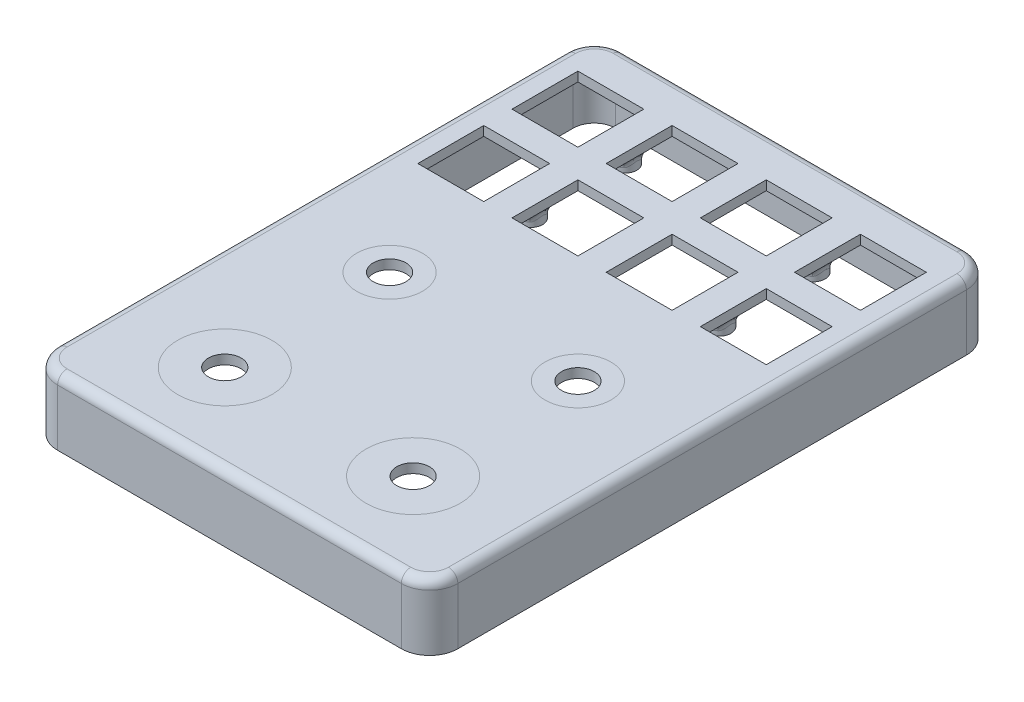
SolidWorks part; units mm, degrees
ref_plane "Plan de face" through (0, 0, 0) normal (0, 0, 1) x (1, 0, 0)
ref_plane "Plan de dessus" through (0, 0, 0) normal (0, 1, 0) x (1, 0, 0)
ref_plane "Plan de droite" through (0, 0, 0) normal (1, 0, 0) x (0, 0, -1)
sketch "Esquisse1" plane through (0, 0, 0) normal (0, 1, 0) x (1, 0, 0)
  line L1 (-42.5, -60) -> (42.5, -60)
  line L2 (-42.5, -60) -> (-42.5, 60)
  line L3 (-42.5, 60) -> (42.5, 60)
  line L4 (42.5, -60) -> (42.5, 60)
  line L5 (-42.5, -60) -> (42.5, 60) construction
  line L6 (-42.5, 60) -> (42.5, -60) construction
  point P0 (0, 0)
  dimension "D1" = 85
  dimension "D2" = 120
extrude "Boss.-Extru.1" add sketch "Esquisse1" along normal blind 2
sketch "Esquisse2" plane through (0, 2, 0) normal (0, 1, 0) x (1, 0, 0)
  line L0 (42.5, 60) -> (-42.5, 60) construction
  line L1 (-37, 51) -> (-23, 51)
  line L2 (-37, 51) -> (-37, 37)
  line L3 (-37, 37) -> (-23, 37)
  line L4 (-23, 51) -> (-23, 37)
  line L5 (-37, 51) -> (-23, 37) construction
  line L6 (-37, 37) -> (-23, 51) construction
  line L7 (-17, 51) -> (-3, 51)
  line L8 (-17, 51) -> (-17, 37)
  line L9 (-17, 37) -> (-3, 37)
  line L10 (-3, 51) -> (-3, 37)
  line L11 (-17, 51) -> (-3, 37) construction
  line L12 (-17, 37) -> (-3, 51) construction
  line L13 (3, 51) -> (17, 51)
  line L14 (3, 51) -> (3, 37)
  line L15 (3, 37) -> (17, 37)
  line L16 (17, 51) -> (17, 37)
  line L17 (3, 51) -> (17, 37) construction
  line L18 (3, 37) -> (17, 51) construction
  line L19 (23, 51) -> (37, 51)
  line L20 (23, 51) -> (23, 37)
  line L21 (23, 37) -> (37, 37)
  line L22 (37, 51) -> (37, 37)
  line L23 (23, 51) -> (37, 37) construction
  line L24 (23, 37) -> (37, 51) construction
  line L25 (23, 31) -> (37, 31)
  line L26 (23, 31) -> (23, 17)
  line L27 (23, 17) -> (37, 17)
  line L28 (37, 31) -> (37, 17)
  line L29 (23, 31) -> (37, 17) construction
  line L30 (23, 17) -> (37, 31) construction
  line L31 (17, 31) -> (3, 31)
  line L32 (17, 31) -> (17, 17)
  line L33 (17, 17) -> (3, 17)
  line L34 (3, 31) -> (3, 17)
  line L35 (17, 31) -> (3, 17) construction
  line L36 (17, 17) -> (3, 31) construction
  line L37 (-3, 31) -> (-17, 31)
  line L38 (-3, 31) -> (-3, 17)
  line L39 (-3, 17) -> (-17, 17)
  line L40 (-17, 31) -> (-17, 17)
  line L41 (-3, 31) -> (-17, 17) construction
  line L42 (-3, 17) -> (-17, 31) construction
  line L43 (-37, 31) -> (-23, 31)
  line L44 (-37, 31) -> (-37, 17)
  line L45 (-37, 17) -> (-23, 17)
  line L46 (-23, 31) -> (-23, 17)
  line L47 (-37, 31) -> (-23, 17) construction
  line L48 (-37, 17) -> (-23, 31) construction
  point P0 (-30, 44)
  point P5 (-10, 44)
  point P10 (10, 44)
  point P15 (30, 44)
  point P20 (30, 24)
  point P25 (10, 24)
  point P30 (-10, 24)
  point P35 (-30, 24)
  dimension "D1" = 14
  dimension "D2" = 14
  dimension "D3" = 20
  dimension "D4" = 20
  dimension "D5" = 20
  dimension "D6" = 10
  dimension "D7" = 16
  dimension "D8" = 20
extrude "Enlèv. mat.-Extru.1" cut sketch "Esquisse2" against normal blind 2
sketch "Esquisse3" plane through (0, 2, 0) normal (0, 1, 0) x (1, 0, 0)
  circle A0 centre (-20, -6) radius 7
  circle A1 centre (-20, -41) radius 10
  circle A2 centre (20, -6) radius 7
  circle A3 centre (20, -41) radius 10
  dimension "D1" = 14
  dimension "D6" = 20
  dimension "D2" = 35
  dimension "D3" = 20
  dimension "D4" = 20
  dimension "D5" = 6
extrude "Enlèv. mat.-Extru.2" cut sketch "Esquisse3" against normal blind 2
fillet "Congé1" radius 6 4 edges at (42.5, 1, 60) (-42.5, 1, 60) (-42.5, 1, -60) (42.5, 1, -60)
sketch "Esquisse5" plane through (0, 0, 0) normal (0, -1, 0) x (1, 0, 0)
  line L0 (-17, -31) -> (-17, -17) construction
  line L1 (-17, -51) -> (-17, -37) construction
  circle A0 centre (-20, -24) radius 2.5
  circle A1 centre (-20, -44) radius 2.5
  circle A3 centre (20, -44) radius 2.5
  circle A4 centre (20, -24) radius 2.5
  circle A7 centre (-20, -24) radius 0.95
  circle A9 centre (20, -24) radius 0.95
  circle A10 centre (20, -44) radius 0.95
  circle A12 centre (-20, -44) radius 0.95
  point P4 (20, -24)
  point P5 (0, 0)
  point P10 (0, 0)
  point P11 (20, -24)
  point P20 (-17, -24)
  point P23 (-17, -44)
  dimension "D1" = 5
  dimension "D4" = 1.9
  dimension "D2" = 20
  dimension "D3" = 20
extrude "Boss.-Extru.3" add sketch "Esquisse5" along normal blind 3
fillet "Congé2" radius 2 4 edges at (-20, 0, -46.5) (-20, 0, -26.5) (20, 0, -46.5) (20, 0, -26.5)
sketch "Esquisse6" plane through (0, 0, 0) normal (0, -1, 0) x (1, 0, 0)
  line L18 (-36.5, -58.5) -> (36.5, -58.5)
  line L19 (-42.5, -54) -> (-42.5, 54) construction
  line L20 (-36.5, 60) -> (36.5, 60) construction
  line L21 (41, -54) -> (41, 54)
  line L22 (36.5, 58.5) -> (-36.5, 58.5)
  line L23 (-41, 54) -> (-41, -54)
  line L24 (41, -54) -> (41, 54)
  line L25 (36.5, 58.5) -> (-36.5, 58.5)
  line L26 (-41, 54) -> (-41, -54)
  line L27 (42.5, 54) -> (42.5, -54) construction
  line L28 (36.5, -60) -> (-36.5, -60) construction
  line L29 (-42.5, -54) -> (-42.5, 54)
  line L30 (-36.5, 60) -> (36.5, 60)
  line L31 (42.5, 54) -> (42.5, -54)
  line L32 (36.5, -60) -> (-36.5, -60)
  arc A19 (-42.5, -54) -> (-36.5, -60) centre (-36.5, -54) ccw construction
  arc A20 (-36.5, 60) -> (-42.5, 54) centre (-36.5, 54) ccw construction
  arc A21 (42.5, 54) -> (36.5, 60) centre (36.5, 54) ccw construction
  arc A22 (36.5, -60) -> (42.5, -54) centre (36.5, -54) ccw construction
  arc A23 (-41, -54) -> (-36.5, -58.5) centre (-36.5, -54) ccw
  arc A24 (36.5, -58.5) -> (41, -54) centre (36.5, -54) ccw
  arc A25 (41, 54) -> (36.5, 58.5) centre (36.5, 54) ccw
  arc A26 (-36.5, 58.5) -> (-41, 54) centre (-36.5, 54) ccw
  arc A27 (-41, -54) -> (-36.5, -58.5) centre (-36.5, -54) ccw
  arc A28 (36.5, -58.5) -> (41, -54) centre (36.5, -54) ccw
  arc A29 (41, 54) -> (36.5, 58.5) centre (36.5, 54) ccw
  arc A30 (-36.5, 58.5) -> (-41, 54) centre (-36.5, 54) ccw
  arc A31 (-42.5, -54) -> (-36.5, -60) centre (-36.5, -54) ccw
  arc A32 (-36.5, 60) -> (-42.5, 54) centre (-36.5, 54) ccw
  arc A33 (42.5, 54) -> (36.5, 60) centre (36.5, 54) ccw
  arc A34 (36.5, -60) -> (42.5, -54) centre (36.5, -54) ccw
  dimension "D1" = 1.5
extrude "Boss.-Extru.4" add sketch "Esquisse6" along normal blind 12
sketch "Esquisse7" plane through (0, 0, 0) normal (0, -1, 0) x (1, 0, 0)
  line L0 (-42.5, 54) -> (-42.5, -54) construction
  line L1 (36.5, 60) -> (-36.5, 60) construction
  line L2 (42.5, -54) -> (42.5, 54) construction
  circle A0 centre (-35.93, 49.1) radius 4
  circle A1 centre (35.93, 49.1) radius 4
  circle A2 centre (-35.93, 49.1) radius 2.15
  circle A3 centre (35.93, 49.1) radius 2.15
  dimension "D1" = 6.57
  dimension "D4" = 8
  dimension "D5" = 4.3
  dimension "D2" = 10.9
  dimension "D3" = 6.57
extrude "Boss.-Extru.5" add sketch "Esquisse7" along normal blind 6
fillet "Congé5" radius 2 8 edges at (39.682, 0, 57.182) (41, 0, 0) (39.682, 0, -57.182) (0, 0, -58.5) (-39.682, 0, -57.182) (-41, 0, 0) (-39.682, 0, 57.182) (0, 0, 58.5)
sketch "Esquisse9" plane through (0, 2, 0) normal (0, 1, 0) x (1, 0, 0)
  circle A0 centre (-20, -41) radius 10 construction
  circle A1 centre (20, -41) radius 10 construction
  circle A2 centre (20, -6) radius 7 construction
  circle A3 centre (-20, -6) radius 7 construction
  circle A4 centre (-20, -41) radius 10
  circle A5 centre (20, -41) radius 10
  circle A6 centre (20, -6) radius 7
  circle A7 centre (-20, -6) radius 7
  circle A8 centre (-20, -6) radius 3.475
  circle A9 centre (-20, -41) radius 3.475
  circle A10 centre (20, -41) radius 3.475
  circle A11 centre (20, -6) radius 3.475
  dimension "D1" = 6.95
extrude "Boss.-Extru.6" add sketch "Esquisse9" against normal blind 2 separate body
fillet "Congé6" radius 2 8 edges at (40.7426, 2, 58.2426) (0, 2, 60) (-40.7426, 2, 58.2426) (-42.5, 2, 0) (-40.7426, 2, -58.2426) (0, 2, -60) (40.7426, 2, -58.2426) (42.5, 2, 0)
